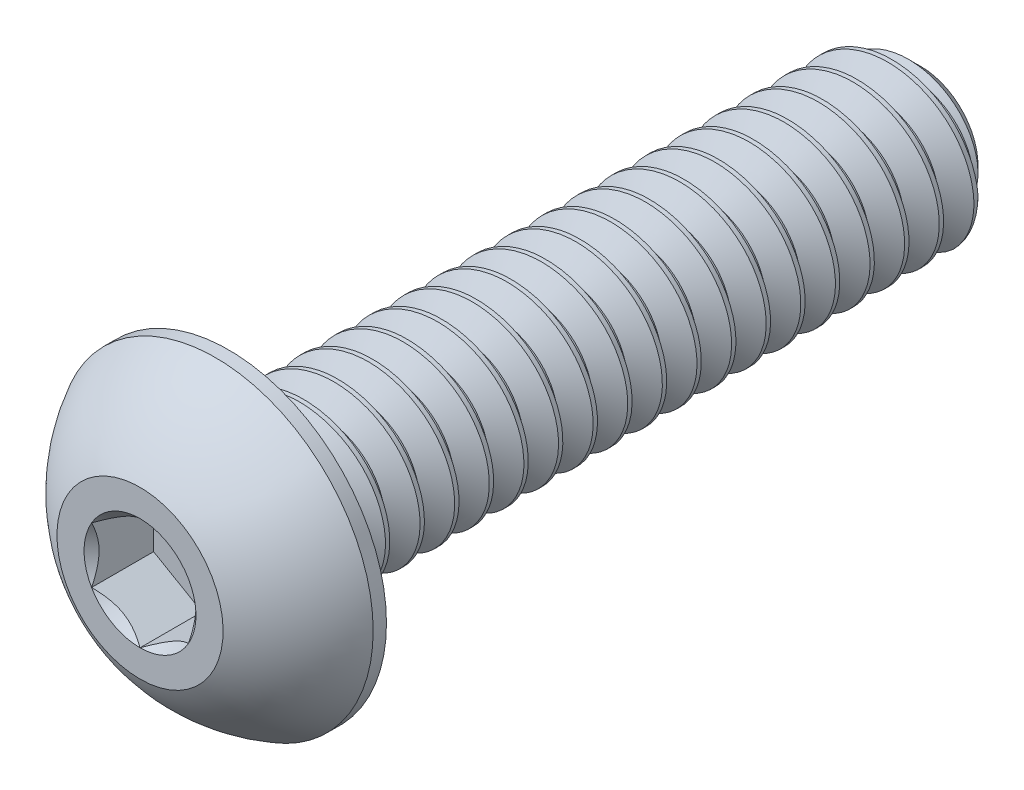
SolidWorks part; units mm, degrees
ref_plane "Front" through (0, 0, 0) normal (0, 0, 1) x (1, 0, 0)
ref_plane "Top" through (0, 0, 0) normal (0, 1, 0) x (1, 0, 0)
ref_plane "Right" through (0, 0, 0) normal (1, 0, 0) x (0, 0, -1)
sketch "Sketch1" plane through (0, 0, 0) normal (1, 0, 0) x (0, 0, -1)
  line L2 (0.8128, 0.762) -> (7.1628, 0.762)
  line L3 (7.1628, 0.762) -> (7.1628, 0)
  line L4 (7.1628, 0) -> (0.8128, 0)
  line L6 (0.6909, 1.4478) -> (0.8128, 1.4478) construction
  line L7 (7.1628, 0.762) -> (7.1628, -0.762) construction
  line L8 (0, 0) -> (0.8128, 0) construction
  line L9 (0.8128, 1.4478) -> (0.8128, -1.4478) construction
  line L11 (0.8128, 0.762) -> (0.8128, 0)
  line L13 (0, 0.4445) -> (0, -0.4445) construction
  line L14 (0, 0.4445) -> (0, 0.762) construction
  arc A3 (0, 0.762) -> (0.6909, 1.4478) centre (1.4422, 0) cw construction
  dimension "D1" = 0.1219
revolve "Revolve1" add sketch "Sketch1" angle 360 mid plane about L4
sketch "Sketch3" plane through (0, 0, -7.1628) normal (0, 0, -1) x (-1, 0, 0)
  circle A0 centre (0, 0) radius 0.762
curve "Helix/Spiral1" pitch 0.3175 height 7.62 radius 0.762 centre (0, 0, -7.1628) axis (0, 0, 1) start towards (0, 1, 0)
sketch "Sketch2" plane through (0, 0, 0) normal (1, 0, 0) x (0, 0, -1)
  line L0 (7.1628, 0.762) -> (7.4406, 0.762)
  line L1 (7.4406, 0.762) -> (7.3216, 0.5558)
  line L2 (7.3216, 0.5558) -> (7.2819, 0.5558)
  line L3 (7.2819, 0.5558) -> (7.1628, 0.762)
  line L4 (7.2223, 0.6589) -> (7.3811, 0.6589) construction
  dimension "D1" = 60
  dimension "D2" = 0.0397
  dimension "D3" = 0.1588
chamfer "Chamfer1" distance 0.2381 angle 45 1 edges at (0, 0.762, -7.1628)
sweep "Cut-Sweep1" cut profiles "Sketch2" path "Helix/Spiral1" align with end faces yes
sketch "Sketch7" plane through (0, 0, 0) normal (1, 0, 0) x (0, 0, -1)
  line L6 (0.6909, 1.4478) -> (0.8128, 1.4478) construction
  line L8 (0, 0) -> (0.8128, 0) construction
  line L11 (0.8128, 1.4478) -> (0.8128, -1.4478) construction
  line L12 (0.6909, 1.4478) -> (0.8128, 1.4478)
  line L13 (0, 0) -> (0.8128, 0)
  line L14 (0, 0.4445) -> (0, -0.4445) construction
  line L15 (0.8128, 1.4478) -> (0.8128, 0)
  line L16 (0, 0.762) -> (0, 0)
  arc A2 (0.6909, 1.4478) -> (0, 0.762) centre (1.4422, 0) ccw construction
  arc A3 (0.6909, 1.4478) -> (0, 0.762) centre (1.4422, 0) ccw
revolve "Revolve2" add sketch "Sketch7" angle 360 mid plane about L13
sketch "Sketch5" plane through (0, 0, 0) normal (0, 0, 1) x (1, 0, 0)
  line L1 (0.4445, -0.2566) -> (0.4445, 0.2566)
  line L2 (0.4445, 0.2566) -> (0, 0.5133)
  line L3 (0, 0.5133) -> (-0.4445, 0.2566)
  line L4 (-0.4445, 0.2566) -> (-0.4445, -0.2566)
  line L5 (-0.4445, -0.2566) -> (0, -0.5133)
  line L6 (0, -0.5133) -> (0.4445, -0.2566)
  circle A0 centre (0, 0) radius 0.4445 construction
extrude "Cut-Extrude2" cut sketch "Sketch5" against normal blind 0.569
sketch "Sketch6" plane through (0, 0, 0) normal (0, 0, 1) x (1, 0, 0)
  circle A0 centre (0, 0) radius 0.5133
extrude "Cut-Extrude3" cut sketch "Sketch6" against normal blind 0.569 draft 45
sketch "Sketch9" [suppressed] plane through (0, 0, -8.2296) normal (0, 0, 1) x (1, 0, 0)
  circle A2 centre (0, 0) radius 7.9375
extrude "Boss-Extrude2" [suppressed] add sketch "Sketch9" against normal offset from surface (25.4 mm away) 22.225 up to face at (0, 0.5239, -7.1628)
sketch "Sketch10" plane through (0, 0, 0) normal (1, 0, 0) x (0, 0, -1)
  line L0 (7.1628, 0.762) -> (7.1628, -0.762) construction
  point P0 (6.6866, -0.762)
  dimension "D1" = 0.4763
equation "\"D2@Sketch2\" = \"D4@Helix/Spiral1\" * .125"
equation "\"D3@Sketch2\" = \"D4@Helix/Spiral1\" * .5"
equation "\"D1@Chamfer1\" = \"D4@Helix/Spiral1\" * .75"
equation "\"D1@Cut-Extrude2\" = \"Head Ht@Sketch1\" * .7"
equation "\"D1@Sketch1\" = \"Head Ht@Sketch1\" * .15"
equation "\"D1@Sketch10\" = \"D4@Helix/Spiral1\" * 1.5"
equation "\"D1@Cut-Extrude3\" = \"D1@Cut-Extrude2\""
